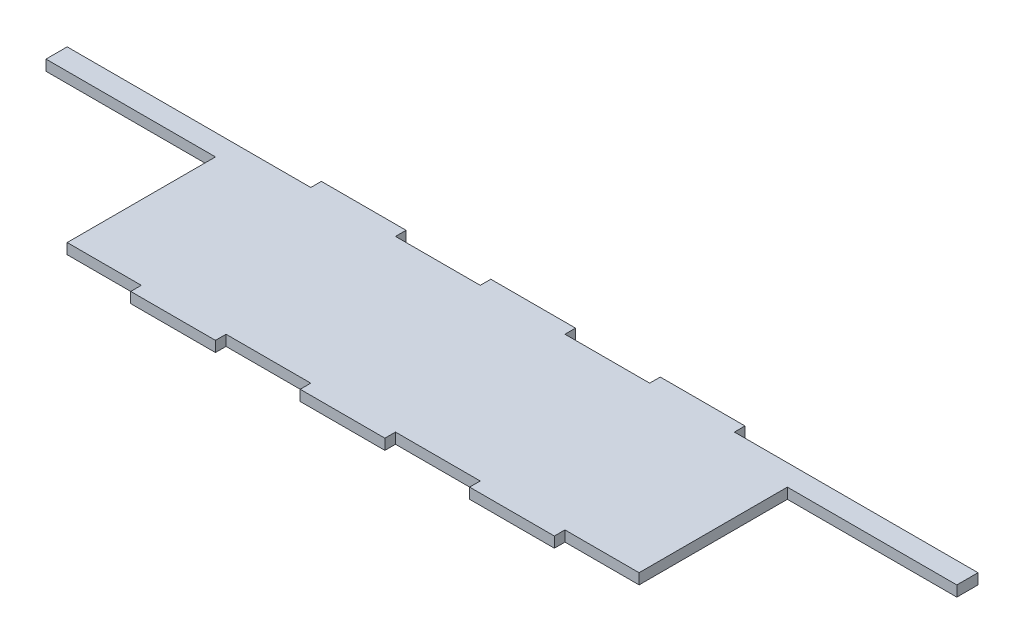
SolidWorks part; units mm, degrees
ref_plane "Front Plane" through (0, 0, 0) normal (0, 0, 1) x (1, 0, 0)
ref_plane "Top Plane" through (0, 0, 0) normal (0, 1, 0) x (1, 0, 0)
ref_plane "Right Plane" through (0, 0, 0) normal (1, 0, 0) x (0, 0, -1)
sketch "Sketch1" plane through (0, 0, 0) normal (0, 1, 0) x (1, 0, 0)
  line L0 (-136.525, 19.05) -> (-85.725, 19.05)
  line L1 (-136.525, -25.4) -> (136.525, -25.4)
  line L2 (-136.525, -25.4) -> (-136.525, 25.4)
  line L3 (-136.525, 25.4) -> (136.525, 25.4)
  line L4 (136.525, -25.4) -> (136.525, 25.4)
  line L5 (-136.525, -25.4) -> (136.525, 25.4) construction
  line L6 (-136.525, 25.4) -> (136.525, -25.4) construction
  line L7 (-85.725, 19.05) -> (-85.725, -25.4)
  line L8 (136.525, 19.05) -> (85.725, 19.05)
  line L9 (85.725, 19.05) -> (85.725, -25.4)
  line L10 (-38.1, 28.575) -> (-12.7, 28.575) construction
  line L11 (-63.5, 25.4) -> (-38.1, 25.4)
  line L12 (-63.5, 25.4) -> (-63.5, 28.575)
  line L13 (-63.5, 28.575) -> (-38.1, 28.575)
  line L14 (-38.1, 25.4) -> (-38.1, 28.575)
  line L15 (-12.7, 25.4) -> (12.7, 25.4)
  line L16 (-12.7, 25.4) -> (-12.7, 28.575)
  line L17 (-12.7, 28.575) -> (12.7, 28.575)
  line L18 (12.7, 25.4) -> (12.7, 28.575)
  line L19 (38.1, 25.4) -> (63.5, 25.4)
  line L20 (38.1, 25.4) -> (38.1, 28.575)
  line L21 (38.1, 28.575) -> (63.5, 28.575)
  line L22 (63.5, 25.4) -> (63.5, 28.575)
  line L23 (12.7, 28.575) -> (38.1, 28.575) construction
  line L24 (-38.1, -28.575) -> (-12.7, -28.575) construction
  line L25 (-63.5, -25.4) -> (-38.1, -25.4)
  line L26 (-63.5, -25.4) -> (-63.5, -28.575)
  line L27 (-63.5, -28.575) -> (-38.1, -28.575)
  line L28 (-38.1, -25.4) -> (-38.1, -28.575)
  line L29 (-12.7, -25.4) -> (12.7, -25.4)
  line L30 (-12.7, -25.4) -> (-12.7, -28.575)
  line L31 (-12.7, -28.575) -> (12.7, -28.575)
  line L32 (12.7, -25.4) -> (12.7, -28.575)
  line L33 (38.1, -25.4) -> (63.5, -25.4)
  line L34 (38.1, -25.4) -> (38.1, -28.575)
  line L35 (38.1, -28.575) -> (63.5, -28.575)
  line L36 (63.5, -25.4) -> (63.5, -28.575)
  line L37 (12.7, -28.575) -> (38.1, -28.575) construction
  point P0 (0, 0)
  point P24 (0, 28.575)
  dimension "D1" = 50.8
  dimension "D2" = 273.05
  dimension "D3" = 44.45
  dimension "D4" = 50.8
  dimension "D5" = 3.175
  dimension "D6" = 25.4
extrude "Boss-Extrude1" add sketch "Sketch1" along normal blind 3.175 contours L9 L8 L4 L3 L2 L0 L7 L1 | L26 L25 L28 L27 | L30 L29 L32 L31 | L34 L33 L36 L35 | L20 L19 L22 L21 | L16 L15 L18 L17 | L12 L11 L14 L13 region at (0, 0, -1.5328)
